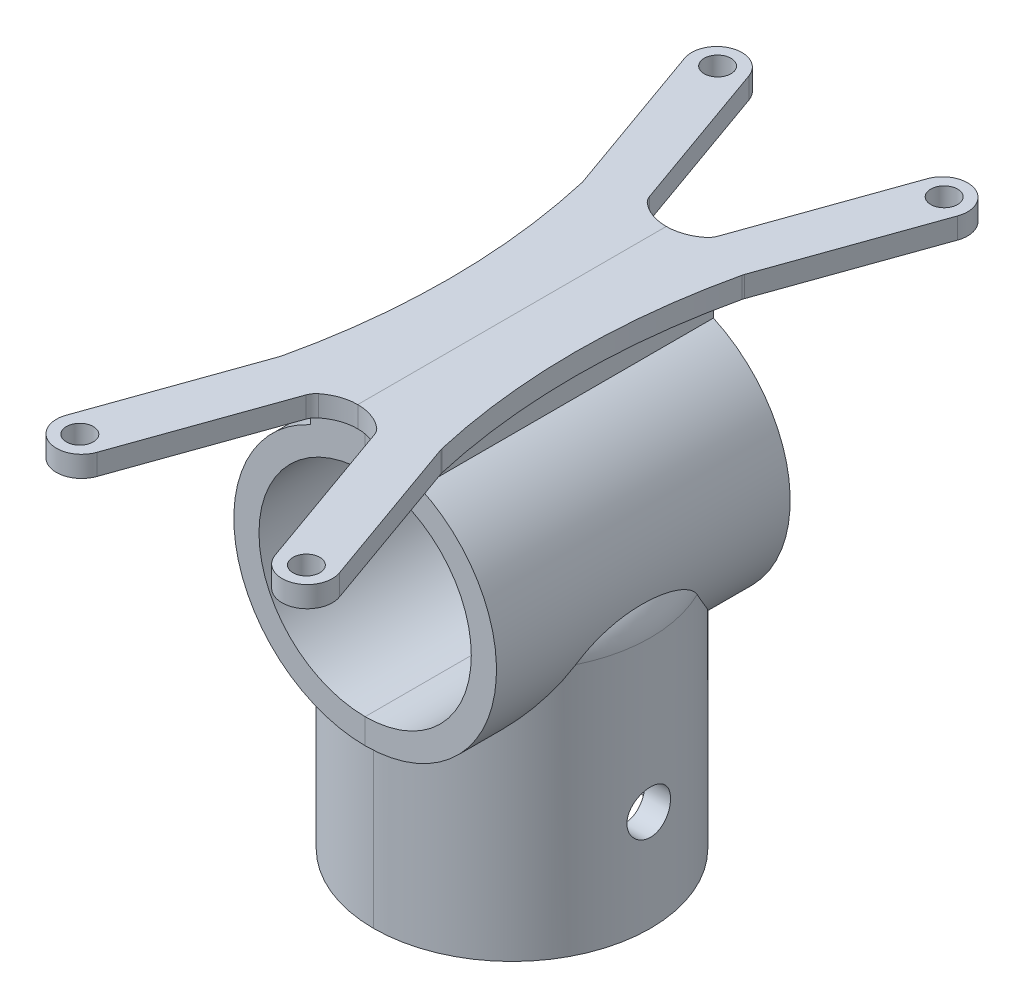
SolidWorks part; units mm, degrees
ref_plane "Front Plane" through (0, 0, 0) normal (0, 0, 1) x (1, 0, 0)
ref_plane "Top Plane" through (0, 0, 0) normal (0, 1, 0) x (1, 0, 0)
ref_plane "Right Plane" through (0, 0, 0) normal (1, 0, 0) x (0, 0, -1)
sketch "Sketch1" plane through (0, 0, 0) normal (0, 0, 1) x (1, 0, 0)
  circle A0 centre (0, 0) radius 12.65
  circle A1 centre (0, 0) radius 15.65
  dimension "D1" = 25.3
  dimension "D2" = 3
extrude "Boss-Extrude1" add sketch "Sketch1" along normal mid plane 35
ref_plane "Plane1" through (0, -35, 0) normal (0, 1, 0) x (1, 0, 0)
sketch "Sketch2" plane through (0, -35, 0) normal (0, 1, 0) x (1, 0, 0)
  circle A1 centre (0, 0) radius 13.5
  circle A2 centre (0, 0) radius 16.5
  dimension "D1" = 3
  dimension "D2" = 27
ref_plane "Plane3" through (0, 20, 0) normal (0, 1, 0) x (1, 0, 0)
sketch "Sketch4" plane through (0, 20, 0) normal (0, 1, 0) x (1, 0, 0)
  line L0 (-13.5, 0) -> (13.5, 0) construction
  line L1 (-13.5, -38) -> (-13.5, 38) construction
  line L2 (13.5, -38) -> (13.5, 38) construction
  line L4 (-10, -12.5) -> (10, -12.5)
  line L5 (-10, -12.5) -> (-10, 12.5)
  line L6 (-10, 12.5) -> (10, 12.5)
  line L7 (10, -12.5) -> (10, 12.5)
  line L8 (-10, -12.5) -> (10, 12.5) construction
  line L9 (-10, 12.5) -> (10, -12.5) construction
  circle A0 centre (-13.5, 38) radius 1.6
  circle A1 centre (13.5, 38) radius 1.6
  circle A2 centre (-13.5, -38) radius 1.6
  circle A3 centre (13.5, -38) radius 1.6
  point P4 (0, 0)
  point P8 (-13.5, 0)
  point P11 (13.5, 0)
  point P12 (13.5, 0)
  point P16 (0, 0)
  dimension "D3" = 3.2
  dimension "D1" = 27
  dimension "D2" = 76
  dimension "D4" = 20
  dimension "D5" = 25
sketch "Sketch5" plane through (0, 20, 0) normal (0, 1, 0) x (1, 0, 0)
  line L0 (-13.5, -38) -> (0, 0) construction
  line L1 (0, 0) -> (13.5, -38) construction
  line L2 (0, 0) -> (-13.5, 38) construction
  line L3 (0, 0) -> (13.5, 38) construction
  line L4 (-9.5769, 17.9957) -> (-3.9231, 20.0043) construction
  line L5 (-3.9231, 20.0043) -> (-10.6184, 38.8503)
  line L6 (-9.5769, 17.9957) -> (-16.2722, 36.8417)
  line L7 (0, 0) -> (0, 17.9957) construction
  line L8 (3.9231, 20.0043) -> (10.6184, 38.8503)
  line L9 (9.5769, 17.9957) -> (16.2722, 36.8417)
  line L10 (0, 0) -> (19.5583, 0) construction
  line L11 (9.5769, -17.9957) -> (16.2722, -36.8417)
  line L12 (3.9231, -20.0043) -> (10.6184, -38.8503)
  line L13 (-3.9231, -20.0043) -> (-10.6184, -38.8503)
  line L14 (-9.5769, -17.9957) -> (-16.2722, -36.8417)
  line L15 (-3.9231, 20.0043) -> (0, 8.9615)
  line L16 (0, 8.9615) -> (3.9231, 20.0043)
  line L17 (-9.5769, 17.9957) -> (-3.1837, 0)
  line L18 (-13.5, 0) -> (13.5, 0) construction
  line L19 (-3.1837, 0) -> (-9.5769, -17.9957)
  line L20 (9.5769, 17.9957) -> (3.1837, 0)
  line L21 (9.5769, -17.9957) -> (3.1837, 0)
  line L22 (0, 0) -> (0, -29.3249) construction
  line L23 (-3.9231, -20.0043) -> (0, -8.9615)
  line L24 (0, -8.9615) -> (3.9231, -20.0043)
  circle A0 centre (13.5, -38) radius 1.6 construction
  circle A1 centre (-13.5, -38) radius 1.6 construction
  circle A2 centre (13.5, 38) radius 1.6 construction
  circle A3 centre (-13.5, 38) radius 1.6 construction
  circle A4 centre (13.5, -38) radius 1.6
  circle A5 centre (-13.5, -38) radius 1.6
  circle A6 centre (13.5, 38) radius 1.6
  circle A7 centre (-13.5, 38) radius 1.6
  arc A8 (-16.2722, 36.8417) -> (-10.6184, 38.8503) centre (-13.4453, 37.846) cw
  arc A9 (16.2722, 36.8417) -> (10.6184, 38.8503) centre (13.4453, 37.846) ccw
  arc A10 (16.2722, -36.8417) -> (10.6184, -38.8503) centre (13.4453, -37.846) cw
  arc A11 (-16.2722, -36.8417) -> (-10.6184, -38.8503) centre (-13.4453, -37.846) ccw
  arc A12 (-9.5769, 17.9957) -> (-9.5769, -17.9957) centre (-87.5266, 0) cw
  arc A13 (9.5769, 17.9957) -> (9.5769, -17.9957) centre (87.5266, 0) ccw
  arc A14 (-3.9231, -20.0043) -> (3.9231, -20.0043) centre (0, -23.9301) cw
  arc A15 (-3.9231, 20.0043) -> (3.9231, 20.0043) centre (0, 23.9301) ccw
  point P17 (-6.75, 19)
  dimension "D3" = 80
  dimension "D4" = 5.55
  dimension "D1" = 6
  dimension "D2" = 20
extrude "Boss-Extrude4" add sketch "Sketch5" against normal blind 2.5 separate body contours L14 A11 L13 L23 L24 L12 A10 L11 L21 L20 L9 A9 L8 L16 L15 L5 A8 L6 L17 L19 A4 A5 A6 A7 | L17 A12 L19 | A13 L20 L21 | L23 A14 L24 | A15 L15 L16 region at (0, 20, 0) region at (0, 20, -15.5551) region at (-6.4628, 20, 0) region at (6.4628, 20, 0) region at (0, 20, 15.5551)
fillet "Fillet1" radius 2 8 edges at (3.9231, 18.75, 20.0043) (9.5769, 18.75, 17.9957) (-3.9231, 18.75, 20.0043) (-9.5769, 18.75, 17.9957) (-9.5769, 18.75, -17.9957) (9.5769, 18.75, -17.9957) (3.9231, 18.75, -20.0043) (-3.9231, 18.75, -20.0043)
sketch "Sketch6" plane through (0, 17.5, 0) normal (0, -1, 0) x (1, 0, 0)
  line L0 (15.65, 17.5) -> (-15.65, 17.5) construction
  line L1 (6.5, 17.5) -> (-6.5, 17.5)
  line L2 (6.5, 17.5) -> (6.5, -17.5)
  line L3 (6.5, -17.5) -> (-6.5, -17.5)
  line L4 (-6.5, 17.5) -> (-6.5, -17.5)
  line L5 (6.5, 17.5) -> (-6.5, -17.5) construction
  line L6 (6.5, -17.5) -> (-6.5, 17.5) construction
  point P0 (0, 0)
  dimension "D2" = 13
extrude "Boss-Extrude5" add sketch "Sketch6" along normal up to next
extrude "Boss-Extrude7" add sketch "Sketch2" along normal blind 35
sketch "Sketch7" plane through (0, 0, 17.5) normal (0, 0, 1) x (1, 0, 0)
  circle A0 centre (0, 0) radius 12.65 construction
  circle A1 centre (0, 0) radius 12.65
extrude "Cut-Extrude2" cut sketch "Sketch7" against normal through all
fillet "Fillet2" radius 5 2 edges at (-16.5, 0, 0) (16.5, 0, 0)
sketch "Sketch8" plane through (0, 0, 0) normal (1, 0, 0) x (0, 0, -1)
  line L0 (0, -35) -> (0, -23) construction
  line L1 (-16.5, -35) -> (16.5, -35) construction
  circle A0 centre (0, -23) radius 2.6
  dimension "D1" = 5.2
  dimension "D2" = 12
extrude "Cut-Extrude3" cut sketch "Sketch8" against normal mid plane 35
split "Split1" trim tools "Right Plane" bodies to split 110 resulting bodies 111 112
